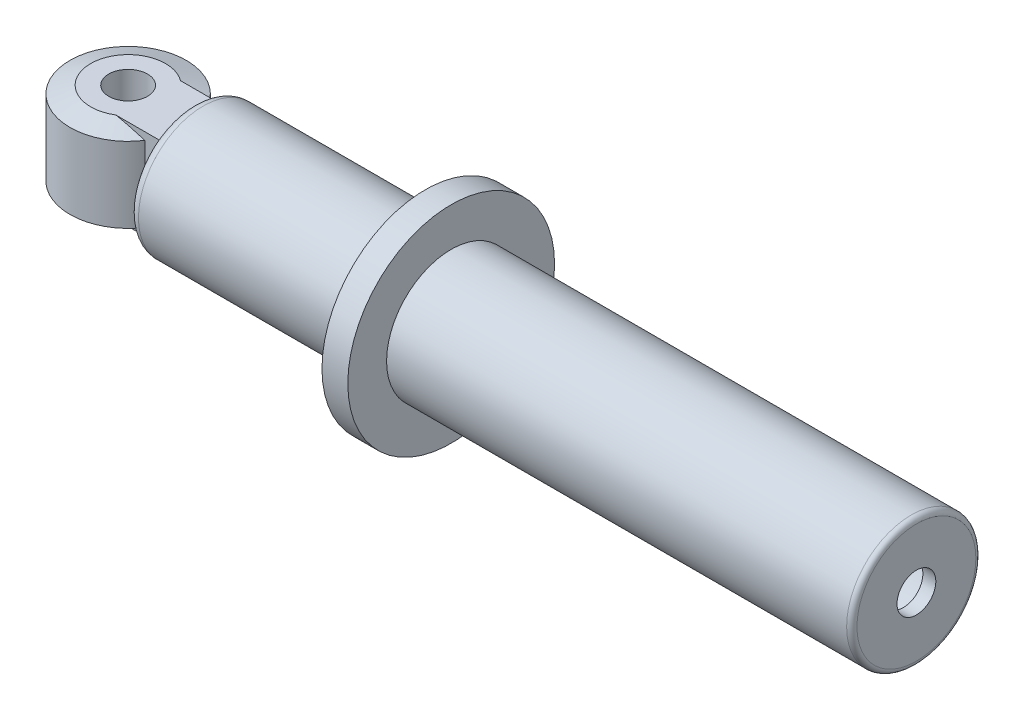
SolidWorks part; units mm, degrees
ref_plane "Front Plane" through (0, 0, 0) normal (0, 0, 1) x (1, 0, 0)
ref_plane "Top Plane" through (0, 0, 0) normal (0, 1, 0) x (1, 0, 0)
ref_plane "Right Plane" through (0, 0, 0) normal (1, 0, 0) x (0, 0, -1)
sketch "Sketch1" plane through (0, 0, 0) normal (0, 1, 0) x (1, 0, 0)
  line L0 (-96.1974, -13.5758) -> (-96.1974, 18.1742)
  line L1 (-96.1974, 18.1742) -> (-39.0474, 18.1742)
  line L2 (-39.0474, 18.1742) -> (-39.0474, 27.6992)
  line L3 (-39.0474, 27.6992) -> (-32.6974, 27.6992)
  line L4 (-32.6974, 27.6992) -> (-32.6974, 18.1742)
  line L5 (-32.6974, 18.1742) -> (81.6026, 18.1742)
  line L6 (81.6026, 18.1742) -> (81.6026, 7.0617)
  line L7 (81.6026, 7.0617) -> (78.4276, 7.0617)
  line L8 (78.4276, 7.0617) -> (78.4276, 14.9992)
  line L9 (78.4276, 14.9992) -> (2.2276, 14.9992)
  line L10 (2.2276, 14.9992) -> (2.2276, -10.4008)
  line L11 (-96.1974, 2.2992) -> (2.2276, 2.2992) construction
  line L12 (78.4276, -10.4008) -> (2.2276, -10.4008)
  line L13 (78.4276, -2.4633) -> (78.4276, -10.4008)
  line L14 (81.6026, -2.4633) -> (78.4276, -2.4633)
  line L15 (81.6026, -13.5758) -> (81.6026, -2.4633)
  line L16 (-32.6974, -13.5758) -> (81.6026, -13.5758)
  line L17 (-32.6974, -23.1008) -> (-32.6974, -13.5758)
  line L18 (-39.0474, -23.1008) -> (-32.6974, -23.1008)
  line L19 (-39.0474, -13.5758) -> (-39.0474, -23.1008)
  line L20 (-96.1974, -13.5758) -> (-39.0474, -13.5758)
  dimension "D1" = 31.75
  dimension "D2" = 25.4
  dimension "D3" = 177.8
  dimension "D4" = 3.175
  dimension "D5" = 9.525
  dimension "D6" = 76.2
  dimension "D7" = 6.35
  dimension "D8" = 9.525
  dimension "D9" = 57.15
revolve "Revolve1" add sketch "Sketch1" angle 360 about L11 region at (-33.1564, 0, -11.4937)
sketch "Sketch2" plane through (0, 0, 0) normal (0, 1, 0) x (1, 0, 0)
  line L0 (-96.1974, 2.2992) -> (-112.0724, 2.2992) construction
  line L1 (-96.1974, 18.1742) -> (-96.1974, -13.5758) construction
  line L2 (-99.8467, 9.6929) -> (-96.1974, 9.6929)
  line L3 (-96.1974, 9.6929) -> (-96.1974, -5.5471)
  line L4 (-96.1974, -5.5471) -> (-100.1323, -5.5471)
  circle A0 centre (-112.0724, 2.2992) radius 4.7625
  arc A1 (-99.8467, 9.6929) -> (-100.1323, -5.5471) centre (-112.0724, 2.2992) ccw
  dimension "D1" = 14.2875
  dimension "D2" = 15.875
  dimension "D3" = 15.24
extrude "Boss-Extrude1" add sketch "Sketch2" along normal mid plane 22.225
fillet "Fillet1" radius 2.54 1 edges at (-96.1974, 0, 13.5758)
chamfer "Chamfer1" distance 5.08 angle 20 2 edges at (-126.3574, -11.1125, -2.5669) (-126.3574, 11.1125, -2.5669) first distance on face at (-101.8549, -11.1125, -2.2721) first distance on face at (-101.8525, 11.1125, -2.1892)
fillet "Fillet2" radius 1.27 1 edges at (81.6026, 0, 13.5758)
